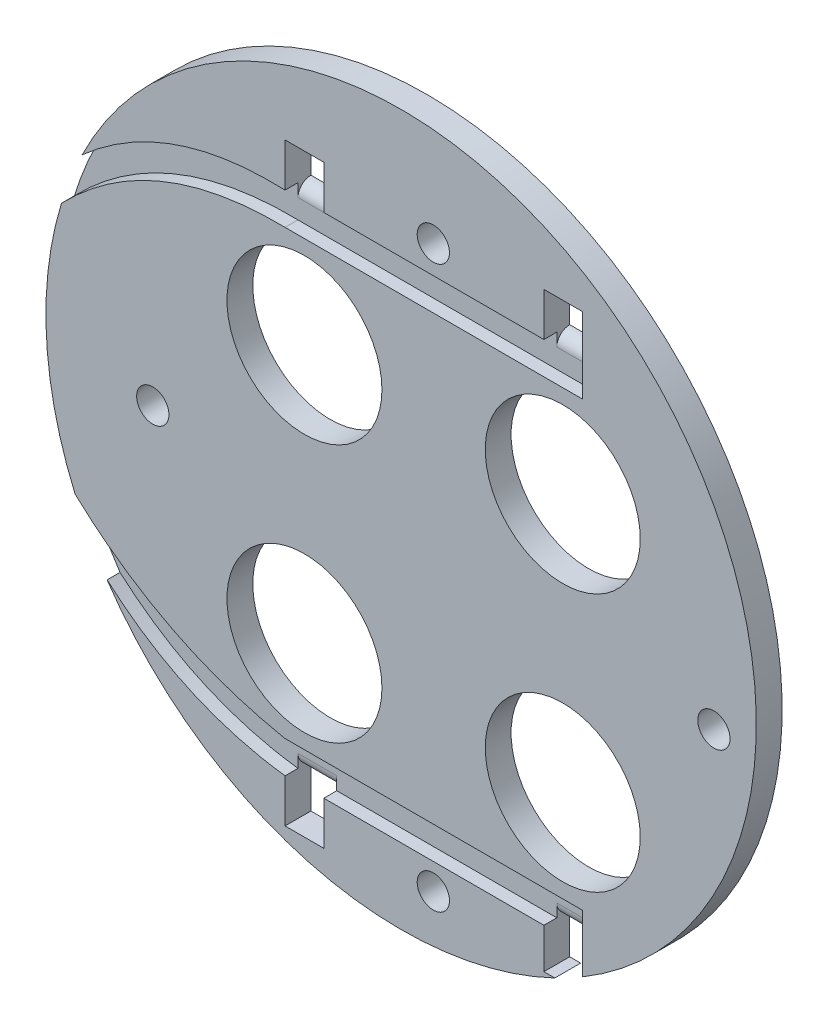
SolidWorks part; units mm, degrees
ref_plane "前视基准面" through (0, 0, 0) normal (0, 0, 1) x (1, 0, 0)
ref_plane "上视基准面" through (0, 0, 0) normal (0, 1, 0) x (1, 0, 0)
ref_plane "右视基准面" through (0, 0, 0) normal (1, 0, 0) x (0, 0, -1)
sketch "Model" plane through (0, 0, 0) normal (0, 0, 1) x (1, 0, 0)
  line L0 (-25.533, -12.6611) -> (-25.5333, -12.6611)
  line L1 (-28.9727, 11.0552) -> (-28.9729, 11.0552)
  line L2 (-27.7752, -6.3856) -> (-27.7754, -6.3856)
  line L3 (-28.8021, -11.9305) -> (-28.8019, -11.9305)
  line L4 (-27.4232, 7.7599) -> (-27.423, 7.7599)
  line L5 (-28.2483, 14.3922) -> (-28.2485, 14.3922)
  line L6 (-5.9858, -25.0407) -> (-8.9858, -25.0407)
  line L7 (-5.9858, -25.0407) -> (-5.9858, -21.6746)
  line L8 (-5.9858, 20.9593) -> (-5.9858, 17.5932)
  line L9 (-8.9858, 20.9593) -> (-5.9858, 20.9593)
  line L10 (-8.9858, 20.9593) -> (-8.9858, 17.5932)
  line L11 (11.0526, -25.0407) -> (11.0526, -21.6806)
  line L12 (13.6093, -25.0407) -> (11.0526, -25.0407)
  line L13 (14.0526, -24.7946) -> (14.0526, -21.6686)
  line L14 (14.0526, 20.9593) -> (14.0526, 17.5871)
  line L15 (11.0526, 20.9593) -> (14.0526, 20.9593)
  line L16 (11.0526, 20.9593) -> (11.0526, 17.5991)
  line L17 (-8.9858, -25.0407) -> (-8.9858, -21.6746)
  line L18 (14.0526, 19.9593) -> (11.0526, 19.9593)
  line L19 (-8.9858, -24.0407) -> (-5.9858, -24.0407)
  line L20 (11.0526, -24.0407) -> (13.6093, -24.0407)
  line L21 (13.6093, -25.0407) -> (13.6093, -24.0407)
  line L22 (-5.9858, 19.9593) -> (-8.9858, 19.9593)
  circle A0 centre (22.2739, 22.2739) radius 1.4
  circle A1 centre (22.2739, -22.2739) radius 1.4
  circle A2 centre (-22.2739, 22.2739) radius 1.4
  circle A3 centre (0, 0) radius 28.5
  circle A4 centre (-22.2739, -22.2739) radius 1.4
  circle A5 centre (-19.2268, -1.9718) radius 0.9
  circle A6 centre (2.4943, 19.7493) radius 0.9
  circle A7 centre (2.4943, -23.6929) radius 0.9
  circle A8 centre (24.2154, -1.9718) radius 0.9
  circle A9 centre (12.5142, 7.9593) radius 4.5
  circle A10 centre (-7.4858, -12.0407) radius 4.5
  circle A11 centre (12.5142, -12.0407) radius 4.5
  circle A12 centre (-7.4858, 7.9593) radius 4.5
  arc A13 (24.6863, 24.6863) -> (-24.6863, 24.6863) centre (0, -30) ccw
  arc A14 (24.6863, -24.6863) -> (24.6863, 24.6863) centre (-30, 0) ccw
  arc A15 (-24.6863, -24.6863) -> (24.6863, -24.6863) centre (0, 30) ccw
  arc A16 (-24.6863, 24.6863) -> (-24.6863, -24.6863) centre (30, 0) ccw
  arc A17 (-5.9858, -21.6746) -> (-8.9858, -21.6746) centre (-7.4858, -12.0407) ccw
  arc A18 (-8.9858, 17.5932) -> (-5.9858, 17.5932) centre (-7.4858, 7.9593) ccw
  arc A19 (11.0526, 17.5991) -> (14.0526, 17.5871) centre (12.5142, 7.9593) ccw
  arc A20 (14.0526, -21.6686) -> (11.0526, -21.6806) centre (12.5142, -12.0407) ccw
  spline S0 degree 3 poles (13.6093, -24.0407) (13.7575, -24.0407) (13.9053, -24.0407) (14.0526, -24.0407) knots 0 0 0 0 1 1 1 1
sketch "草图2" plane through (0, 0, 0) normal (0, 0, 1) x (1, 0, 0)
  circle A0 centre (0, 0) radius 27.5019
  dimension "D1" = 55.0037
extrude "凸台-拉伸1" add sketch "草图2" along normal blind 2
sketch "草图3" plane through (0, 0, 2) normal (0, 0, 1) x (1, 0, 0)
  circle A0 centre (2.4943, 19.7493) radius 1.25
  circle A1 centre (-19.2268, -1.9718) radius 1.25
  circle A2 centre (2.4943, -23.6929) radius 1.25
  circle A3 centre (24.2154, -1.9718) radius 1.25
  dimension "D1" = 2.5
extrude "切除-拉伸1" cut sketch "草图3" against normal blind 2
sketch "草图4" plane through (0, 0, 2) normal (0, 0, 1) x (1, 0, 0)
  circle A0 centre (-7.4858, 7.9593) radius 6
  circle A1 centre (12.5142, 7.9593) radius 6
  circle A2 centre (-7.4858, -12.0407) radius 6
  circle A3 centre (12.5142, -12.0407) radius 6
  dimension "D1" = 12
extrude "切除-拉伸2" cut sketch "草图4" against normal blind 10
sketch "草图5" plane through (0, 0, 2) normal (0, 0, 1) x (1, 0, 0)
  line L1 (-8.9858, 20.9593) -> (-5.9858, 20.9593)
  line L2 (-8.9858, 20.9593) -> (-8.9858, 17.5932)
  line L3 (-8.9858, 17.5932) -> (-5.9858, 17.5932)
  line L4 (-5.9858, 20.9593) -> (-5.9858, 17.5932)
  line L5 (11.0526, 20.9593) -> (14.0526, 20.9593)
  line L6 (11.0526, 20.9593) -> (11.0526, 17.5871)
  line L7 (11.0526, 17.5871) -> (14.0526, 17.5871)
  line L8 (14.0526, 20.9593) -> (14.0526, 17.5871)
  line L9 (-8.9858, -21.6746) -> (-5.9858, -21.6746)
  line L10 (-8.9858, -21.6746) -> (-8.9858, -25.0407)
  line L11 (-8.9858, -25.0407) -> (-5.9858, -25.0407)
  line L12 (-5.9858, -21.6746) -> (-5.9858, -25.0407)
  line L13 (11.0526, -21.6806) -> (14.0526, -21.6806)
  line L14 (11.0526, -21.6806) -> (11.0526, -24.7946)
  line L15 (11.0526, -24.7946) -> (14.0526, -24.7946)
  line L16 (14.0526, -21.6806) -> (14.0526, -24.7946)
extrude "切除-拉伸3" cut sketch "草图5" against normal blind 10
sketch "草图6" plane through (0, 0, 2) normal (0, 0, 1) x (1, 0, 0)
  line L1 (14.0526, -21.6806) -> (-8.9858, -21.6806)
  line L2 (14.0526, -21.6806) -> (14.0526, -19.1806)
  line L3 (14.0526, -19.1806) -> (-8.9858, -19.1806)
  line L5 (14.0526, -21.6806) -> (11.0526, -21.6806) construction
  line L6 (14.0526, 17.5932) -> (-8.9858, 17.5932)
  line L7 (14.0526, 17.5932) -> (14.0526, 15.0932)
  line L8 (14.0526, 15.0932) -> (-8.9858, 15.0932)
  line L11 (-8.9858, 17.5932) -> (-5.9858, 17.5932) construction
  arc A0 (14.0526, -23.6406) -> (11.8987, -24.7946) centre (0, 0) ccw construction
  arc A2 (-25.2375, -10.9281) -> (-22.7653, -15.4303) centre (0, 0) ccw
  arc A3 (14.0526, -23.6406) -> (11.8987, -24.7946) centre (0, 0) ccw
  arc A4 (-24.6938, 12.1066) -> (-26.2948, 8.0582) centre (0, 0) ccw
  spline S0 degree 2 poles (-8.9858, -21.6806) (-16.8259, -20.6751) (-22.7653, -15.4303) knots 0 0 0 1 1 1
  spline S1 degree 2 poles (-8.9858, -19.1806) (-18.3186, -17.354) (-25.2375, -10.9281) knots 0 0 0 1 1 1
  spline S2 degree 2 poles (-8.9858, 17.5932) (-18.1412, 17.9368) (-24.6938, 12.1066) knots 0 0 0 1 1 1
  spline S3 degree 2 poles (-8.9858, 15.0932) (-19.3066, 15.2869) (-26.2948, 8.0582) knots 0 0 0 1 1 1
  dimension "D1" = 2.5
  dimension "D2" = 2.5
  dimension "D3" = 0
extrude "切除-拉伸4" cut sketch "草图6" against normal blind 1
fillet "圆角1" radius 1 4 edges at (-7.4858, -21.6746, 1) (12.5526, -21.6806, 1) (12.5526, 17.5871, 1)
